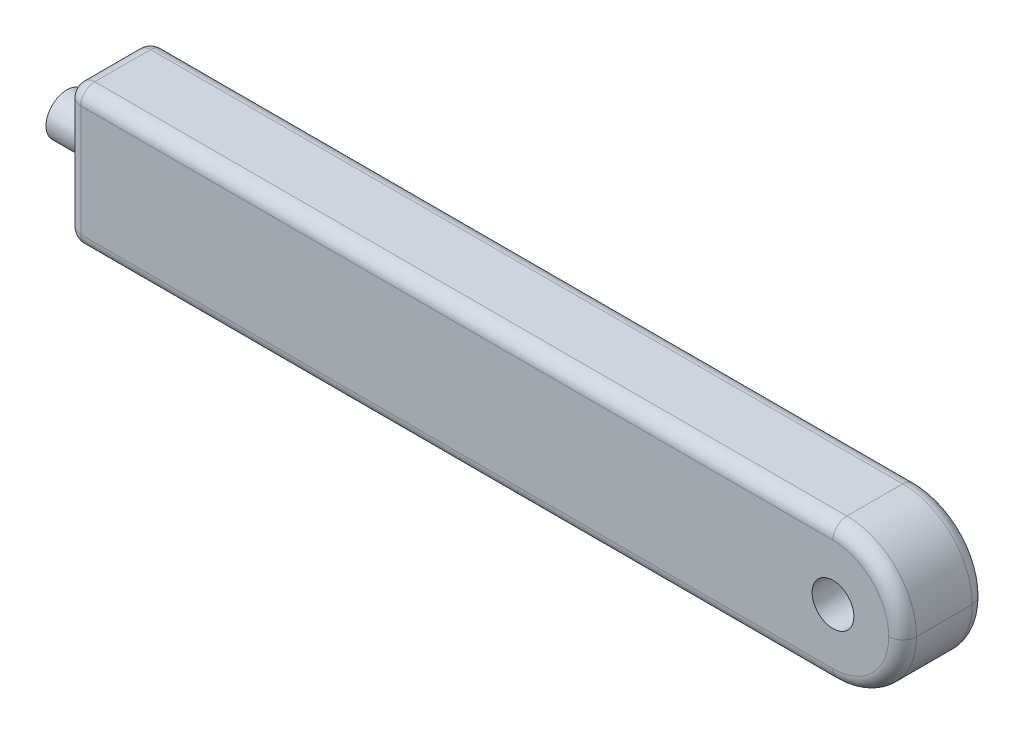
SolidWorks part; units mm, degrees
ref_plane "Alzado" through (0, 0, 0) normal (0, 0, 1) x (1, 0, 0)
ref_plane "Planta" through (0, 0, 0) normal (0, 1, 0) x (1, 0, 0)
ref_plane "Vista lateral" through (0, 0, 0) normal (1, 0, 0) x (0, 0, -1)
sketch "Croquis1" plane through (0, 0, 0) normal (0, 0, 1) x (1, 0, 0)
  line L1 (0, 0) -> (300, 0)
  line L2 (0, 0) -> (0, 50)
  line L3 (0, 50) -> (300, 50)
  line L4 (300, 0) -> (300, 50)
  circle A0 centre (275, 25) radius 7.5
extrude "Saliente-Extruir1" add sketch "Croquis1" along normal blind 30
fillet "Redondeo1" radius 25 2 edges at (300, 0, 15) (300, 50, 15)
sketch "Croquis2" plane through (0, 0, 0) normal (-1, 0, 0) x (0, 0, 1)
  circle A0 centre (15, 25) radius 7.5
extrude "Saliente-Extruir2" add sketch "Croquis2" along normal blind 15
fillet "Redondeo2" radius 5 12 edges at (0, 0, 15) (137.5, 0, 30) (292.6777, 7.3223, 30) (292.6777, 42.6777, 30) (137.5, 50, 30) (0, 25, 30) (0, 50, 15) (0, 25, 0) (137.5, 0, 0) (292.6777, 7.3223, 0) (292.6777, 42.6777, 0) (137.5, 50, 0)
